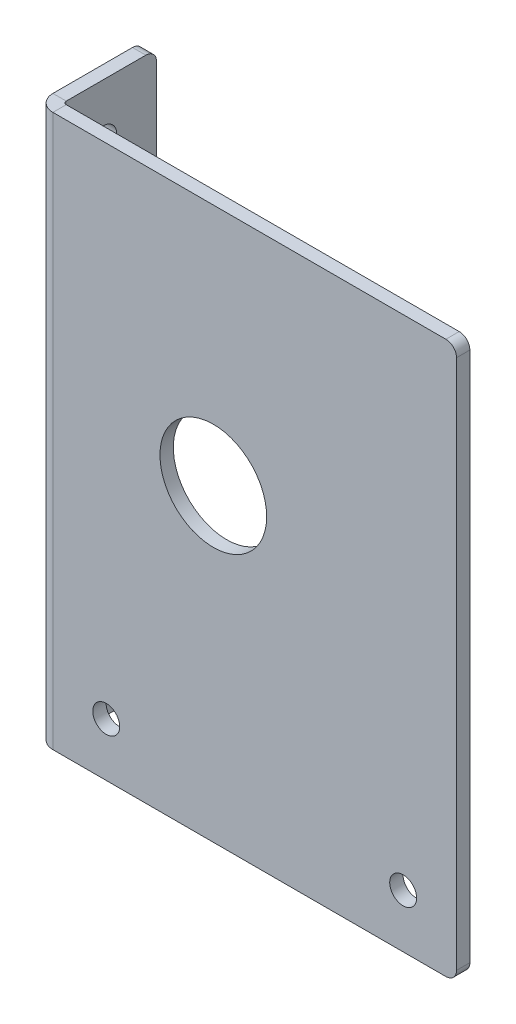
SolidWorks part; units mm, degrees
note: The reader was unsure of these and kept them because the rebuilt part matched: flange length of "Edge-Flange1".
ref_plane "Front Plane" through (0, 0, 0) normal (1, 0, 0) x (0, 1, 0)
ref_plane "Top Plane" through (0, 0, 0) normal (0, 0, 1) x (0, 1, 0)
ref_plane "Right Plane" through (0, 0, 0) normal (0, 1, 0) x (-1, 0, 0)
sketch "Sketch1" plane through (0, 0, 0) normal (0, 0, 1) x (0, 1, 0)
  line L1 (-65.7, 50) -> (65.7, 50)
  line L2 (-65.7, 50) -> (-65.7, -50)
  line L3 (-65.7, -50) -> (65.7, -50)
  line L4 (65.7, 50) -> (65.7, -50)
  line L5 (-65.7, 50) -> (65.7, -50) construction
  line L6 (-65.7, -50) -> (65.7, 50) construction
  point P0 (0, 0)
  dimension "D1" = 131.4
  dimension "D2" = 100
base flange "Base-Flange1" sketch "Sketch1" thickness 3.175 reverse thickness direction yes parameters "D1"=0.7366
edge flange "Edge-Flange1" sketch "Sketch8" flange angle 90 flange length 25.4 flange position material inside bend radius 0.7366 thickness 3.175 relief rectangular parameters "D6"=10
sketch "Sketch8" plane through (-50, 0, 0) normal (-1, 0, 0) x (0, 1, 0)
  line L0 (65.7, 0) -> (-65.7, 0) construction
  line L1 (65.7, 0) -> (-65.7, 0)
  line L2 (-65.7, 0) -> (-65.7, 22.225)
  line L3 (-65.7, 22.225) -> (65.7, 22.225)
  line L4 (65.7, 22.225) -> (65.7, 0)
bend "EdgeBend1" bend radius 0.7366 bend angle 90 parameters "D5"=1
fillet "Fillet1" radius 2.54 4 edges at (50, 65.7, 1.5875) (-48.4125, -65.7, -22.225) (-48.4125, 65.7, -22.225) (50, -65.7, 1.5875)
sketch "Sketch15" plane through (0, 0, 3.175) normal (0, 0, 1) x (1, 0, 0)
  line L2 (-46.0884, -65.7) -> (47.46, -65.7) construction
  line L3 (50, -63.16) -> (50, 63.16) construction
  circle A0 centre (-7.9, 7.8) radius 12.7
  point P0 (0, 0)
  point P2 (0, 0)
  dimension "D2" = 25.4
  dimension "D1" = 57.9
  dimension "D3" = 73.5
extrude "Motor Hole" cut sketch "Sketch15" against normal through all normal cut yes
sketch "Sketch9" plane through (-46.825, 0, 0) normal (1, 0, 0) x (0, 1, 0)
  line L8 (63.16, -22.225) -> (-63.16, -22.225) construction
  line L11 (65.7, -0.7366) -> (65.7, -19.685) construction
  circle A0 centre (53, -9.525) radius 3.205
  dimension "D3" = 6.41
  dimension "D1" = 12.7
  dimension "D2" = 12.7
extrude "Cut-Extrude1" cut sketch "Sketch9" against normal through all normal cut yes
mirror "Mirror1" about plane through (0, 0, 0) normal (0, 1, 0) of "Cut-Extrude1"
sketch "Sketch10" plane through (0, 0, 0) normal (0, 0, -1) x (1, 0, 0)
  line L0 (37.3, 53) -> (50, 53) construction
  line L2 (50, 63.16) -> (50, -63.16) construction
  line L4 (50, -63.16) -> (50, 63.16)
  line L5 (47.46, 65.7) -> (-46.0884, 65.7)
  line L6 (-46.0884, 65.7) -> (-46.0884, -65.7)
  line L7 (-46.0884, -65.7) -> (47.46, -65.7)
  line L8 (50, 22.1937) -> (50, 28.6063) construction
  line L10 (-46.0884, 28.6063) -> (-46.0884, 22.1937) construction
  line L12 (-33.3884, 53) -> (-46.0884, 53) construction
  line L13 (-46.0884, -65.7) -> (-46.0884, 65.7) construction
  line L14 (-33.3884, 53) -> (37.3, 53) construction
  line L15 (-46.0884, 65.7) -> (47.46, 65.7) construction
  circle A0 centre (-33.3884, 53) radius 3.2063
  circle A1 centre (37.3, 53) radius 3.2063
  arc A2 (50, 63.16) -> (47.46, 65.7) centre (47.46, 63.16) ccw
  arc A3 (47.46, -65.7) -> (50, -63.16) centre (47.46, -63.16) ccw
  dimension "D3" = 12.7
  dimension "D4" = 12.7
  dimension "D1" = 0
extrude "Cut-Extrude2" cut sketch "Sketch10" against normal through all normal cut yes
sketch "Bend-Lines1" [suppressed] plane through (0, 0, 0) normal (0, 1, 0) x (1, 0, 0)
sketch "Bounding-Box1" [suppressed] plane through (0, 0, 0) normal (0, 1, 0) x (1, 0, 0)
sheet metal parameters "Sheet-Metal1" thickness 3.175 parameters "D1"=0.7366
flat pattern "Flat-Pattern1" [suppressed]
sketch "Bend-Lines2" plane through (0, 0, 0) normal (0, 1, 0) x (1, 0, 0)
sketch3d "Bounding-Box2" [suppressed]
  line L0 (-38.1, -38.1, 0) -> (38.1, -38.1, 0) construction
  line L1 (-38.1, 38.1, 0) -> (38.1, 38.1, 0) construction
  line L2 (-38.1, -38.1, 0) -> (-38.1, 38.1, 0) construction
  line L3 (38.1, -38.1, 0) -> (38.1, 38.1, 0) construction
sheet metal parameters "Sheet-Metal2" thickness 3.175 parameters "D1"=0.7366
flat pattern "Flat-Pattern1"
sketch "Bend-Lines2" plane through (0, 0, 0) normal (0, 0, -1) x (-1, 0, 0)
  line L0 (36.0137, -38.1) -> (36.0137, 38.1) construction
  line L1 (36.0137, -38.1) -> (36.0137, 38.1) construction
sketch3d "Bounding-Box2" [suppressed]
  line L0 (59.3275, -38.1, 0) -> (-38.1, -38.1, 0) construction
  line L1 (59.3275, 38.1, 0) -> (-38.1, 38.1, 0) construction
  line L2 (59.3275, -38.1, 0) -> (59.3275, 38.1, 0) construction
  line L3 (-38.1, -38.1, 0) -> (-38.1, 38.1, 0) construction
bend of the flat pattern "Flatten-<EdgeBend1>1"
sheet metal parameters "Sheet-Metal3" thickness 3.175 parameters "D1"=0.7366
flat pattern "Flat-Pattern1"
sketch "Bend-Lines2" plane through (0, 0, 0) normal (0, 0, -1) x (-1, 0, 0)
  line L0 (36.0137, -38.1) -> (36.0137, 38.1) construction
  line L1 (36.0137, -38.1) -> (36.0137, 38.1) construction
sketch3d "Bounding-Box2" [suppressed]
  line L0 (59.3275, -38.1, 0) -> (-38.1, -38.1, 0) construction
  line L1 (59.3275, 38.1, 0) -> (-38.1, 38.1, 0) construction
  line L2 (59.3275, -38.1, 0) -> (59.3275, 38.1, 0) construction
  line L3 (-38.1, -38.1, 0) -> (-38.1, 38.1, 0) construction
bend of the flat pattern "Flatten-<EdgeBend1>1"
sheet metal parameters "Sheet-Metal4" thickness 3.175 parameters "D1"=0.7366
flat pattern "Flat-Pattern1"
sketch "Bend-Lines2" plane through (0, 0, 0) normal (0, 0, -1) x (-1, 0, 0)
  line L0 (36.0137, -38.1) -> (36.0137, 38.1) construction
  line L1 (36.0137, -38.1) -> (36.0137, 38.1) construction
sketch3d "Bounding-Box2" [suppressed]
  line L0 (59.3275, -38.1, 0) -> (-38.1, -38.1, 0) construction
  line L1 (59.3275, 38.1, 0) -> (-38.1, 38.1, 0) construction
  line L2 (59.3275, -38.1, 0) -> (59.3275, 38.1, 0) construction
  line L3 (-38.1, -38.1, 0) -> (-38.1, 38.1, 0) construction
bend of the flat pattern "Flatten-<EdgeBend1>1"
sheet metal parameters "Sheet-Metal5" thickness 3.175 parameters "D1"=0.7366
flat pattern "Flat-Pattern1"
sketch "Bend-Lines2" plane through (0, 0, 0) normal (0, 0, -1) x (-1, 0, 0)
  line L0 (47.9137, -65.7) -> (47.9137, 65.7) construction
  line L1 (47.9137, -65.7) -> (47.9137, 65.7) construction
sketch3d "Bounding-Box2" [suppressed]
  line L0 (-50, 65.7, 0) -> (-50, -65.7, 0) construction
  line L1 (71.2275, 65.7, 0) -> (71.2275, -65.7, 0) construction
  line L2 (-50, 65.7, 0) -> (71.2275, 65.7, 0) construction
  line L3 (-50, -65.7, 0) -> (71.2275, -65.7, 0) construction
bend of the flat pattern "Flatten-<EdgeBend1>1"
sheet metal parameters "Sheet-Metal6" thickness 3.175 parameters "D1"=0.7366
flat pattern "Flat-Pattern1"
sketch "Bend-Lines2" plane through (0, 0, 0) normal (0, 0, -1) x (-1, 0, 0)
  line L0 (47.9137, -53) -> (47.9137, 53) construction
  line L1 (47.9137, -53) -> (47.9137, 53) construction
sketch3d "Bounding-Box2" [suppressed]
  line L0 (71.2275, -53, 0) -> (-50, -53, 0) construction
  line L1 (71.2275, 53, 0) -> (-50, 53, 0) construction
  line L2 (71.2275, -53, 0) -> (71.2275, 53, 0) construction
  line L3 (-50, -53, 0) -> (-50, 53, 0) construction
bend of the flat pattern "Flatten-<EdgeBend1>1"
